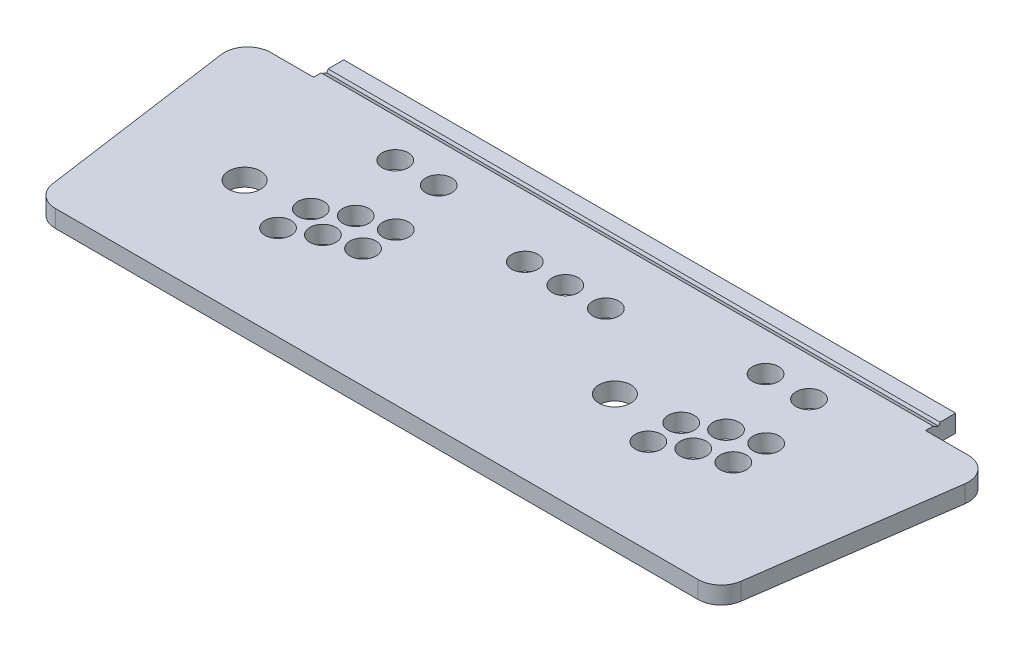
SolidWorks part; units mm, degrees
ref_plane "Front Plane" through (0, 0, 0) normal (0, 0, 1) x (1, 0, 0)
ref_plane "Top Plane" through (0, 0, 0) normal (0, 1, 0) x (1, 0, 0)
ref_plane "Right Plane" through (0, 0, 0) normal (1, 0, 0) x (0, 0, -1)
sketch "Sketch1" plane through (0, 0, 0) normal (0, 1, 0) x (1, 0, 0)
  line L9 (335.7562, 149.733) -> (-335.7563, 149.733)
  line L10 (335.7562, 149.733) -> (335.7562, -149.733)
  line L11 (335.7562, -149.733) -> (-335.7562, -149.733)
  line L12 (-335.7563, 149.733) -> (-335.7562, -149.733)
  line L13 (335.7562, 149.733) -> (-335.7562, -149.733) construction
  line L14 (335.7562, -149.733) -> (-335.7563, 149.733) construction
  point P0 (0, 0)
  dimension "D1" = 299.466
  dimension "D2" = 671.5125
extrude "Boss-Extrude1" add sketch "Sketch1" along normal mid plane 19.05
sketch "Sketch2" plane through (0, 9.525, 0) normal (0, 1, 0) x (1, 0, 0)
  line L0 (335.7562, -149.733) -> (374.6439, -149.733)
  line L1 (374.6439, -149.733) -> (412.0832, 116.6621)
  line L2 (412.0832, 116.6621) -> (335.7562, 116.6621)
  line L3 (335.7562, -149.733) -> (335.7562, 149.733) construction
  line L4 (335.7562, 116.6621) -> (335.7562, -149.733)
  line L5 (412.0832, 116.6621) -> (412.0833, -148.5139) construction
  line L6 (0, 0) -> (0, 149.733) construction
  line L7 (335.7562, 149.733) -> (-335.7563, 149.733) construction
  line L8 (-412.0832, 116.6621) -> (-412.0833, -148.5139) construction
  line L9 (-335.7562, 116.6621) -> (-335.7562, -149.733)
  line L10 (-412.0832, 116.6621) -> (-335.7562, 116.6621)
  line L11 (-374.6439, -149.733) -> (-412.0832, 116.6621)
  line L12 (-335.7562, -149.733) -> (-374.6439, -149.733)
  dimension "D1" = 266.3951
  dimension "D2" = 76.327
  dimension "D3" = 8
  dimension "D4" = 824.1665
extrude "Boss-Extrude2" add sketch "Sketch2" against normal up to surface (19.05 mm away) up to face at (0, -9.525, 0)
fillet "Fillet1" radius 25.4 4 edges at (-412.0832, 0, -116.6621) (-374.6439, 0, 149.733) (412.0832, 0, -116.6621) (374.6439, 0, 149.733)
sketch "Sketch3" plane through (0, 9.525, 0) normal (0, 1, 0) x (1, 0, 0)
  line L0 (-212.087, -46.05) -> (-212.087, -10.05) construction
  line L1 (-180.837, -28.05) -> (-180.837, 7.95) construction
  line L2 (-145.837, -19.05) -> (-145.837, 16.95) construction
  line L3 (-145.837, -19.05) -> (-145.837, -46.05) construction
  line L4 (-180.837, -28.05) -> (-180.837, -46.05) construction
  line L5 (-212.087, -46.05) -> (-180.837, -46.05) construction
  line L6 (-275.837, -19.05) -> (130.563, -19.05) construction
  line L7 (-180.837, -46.05) -> (-145.837, -46.05) construction
  line L8 (-212.087, 82.55) -> (-164.3697, 82.55) construction
  line L9 (-275.837, -19.05) -> (-275.837, 82.55) construction
  line L10 (-145.837, -46.05) -> (-128.5613, -46.05) construction
  line L11 (-212.087, -46.05) -> (-275.837, -46.05) construction
  line L12 (-275.837, 82.55) -> (-212.087, 82.55) construction
  line L13 (-275.837, -19.05) -> (-275.837, -46.05) construction
  line L14 (194.313, -46.05) -> (194.313, -10.05) construction
  line L15 (225.563, -28.05) -> (225.563, 7.95) construction
  line L16 (260.563, -19.05) -> (260.563, 16.95) construction
  line L17 (260.563, -19.05) -> (260.563, -46.05) construction
  line L18 (225.563, -28.05) -> (225.563, -46.05) construction
  line L19 (194.313, -46.05) -> (225.563, -46.05) construction
  line L20 (225.563, -46.05) -> (260.563, -46.05) construction
  line L21 (194.313, 82.55) -> (242.0303, 82.55) construction
  line L22 (130.563, -19.05) -> (130.563, 82.55) construction
  line L23 (194.313, -46.05) -> (130.563, -46.05) construction
  line L24 (130.563, 82.55) -> (194.313, 82.55) construction
  line L25 (130.563, -19.05) -> (130.563, -46.05) construction
  line L26 (-44.45, 57.15) -> (44.45, 57.15) construction
  line L27 (-275.837, -19.05) -> (-275.837, -71.5396) construction
  line L28 (-275.837, -71.5396) -> (-147.2857, -71.5396) construction
  line L29 (-147.2857, -71.5396) -> (-147.2857, -19.05) construction
  line L30 (130.563, -19.05) -> (130.563, -71.5396) construction
  line L31 (130.563, -71.5396) -> (292.5596, -71.5396) construction
  line L32 (-211.5613, -71.5396) -> (-211.5613, -17.7133) construction
  line L33 (211.5613, -71.5396) -> (211.5613, -17.7133) construction
  line L34 (0, -80.6856) -> (0, 57.15) construction
  line L36 (-243.037, 18.9) -> (-308.637, 18.9) construction
  line L37 (-243.037, 18.9) -> (-243.037, -57) construction
  line L38 (-243.037, -57) -> (-308.637, -57) construction
  line L39 (-308.637, 18.9) -> (-308.637, -57) construction
  line L40 (-243.037, 18.9) -> (-308.637, -57) construction
  line L41 (-243.037, -57) -> (-308.637, 18.9) construction
  line L42 (163.363, 18.9) -> (97.763, 18.9) construction
  line L43 (163.363, 18.9) -> (163.363, -57) construction
  line L44 (163.363, -57) -> (97.763, -57) construction
  line L45 (97.763, 18.9) -> (97.763, -57) construction
  line L46 (163.363, 18.9) -> (97.763, -57) construction
  line L47 (163.363, -57) -> (97.763, 18.9) construction
  circle A0 centre (-275.837, -19.05) radius 17.5
  circle A1 centre (-180.837, 7.95) radius 14.2875
  circle A2 centre (-145.837, 16.95) radius 14.2875
  circle A3 centre (-145.837, -19.05) radius 14.2875
  circle A4 centre (-180.837, -28.05) radius 14.2875
  circle A5 centre (-212.087, -10.05) radius 14.2875
  circle A6 centre (-212.087, -46.05) radius 14.2875
  circle A7 centre (-212.087, 82.55) radius 14.2875
  circle A8 centre (-164.3697, 82.55) radius 14.2875
  circle A9 centre (130.563, -19.05) radius 17.5
  circle A10 centre (225.563, 7.95) radius 14.2875
  circle A11 centre (260.563, 16.95) radius 14.2875
  circle A12 centre (260.563, -19.05) radius 14.2875
  circle A13 centre (225.563, -28.05) radius 14.2875
  circle A14 centre (194.313, -10.05) radius 14.2875
  circle A15 centre (194.313, -46.05) radius 14.2875
  circle A16 centre (194.313, 82.55) radius 14.2875
  circle A17 centre (242.0303, 82.55) radius 14.2875
  circle A21 centre (-308.637, 18.9) radius 3.9688
  circle A22 centre (-243.037, 18.9) radius 3.9687
  circle A23 centre (-308.637, -57) radius 3.9688
  circle A24 centre (-243.037, -57) radius 3.9687
  circle A25 centre (97.763, 18.9) radius 3.9687
  circle A26 centre (163.363, 18.9) radius 3.9687
  circle A27 centre (97.763, -57) radius 3.9688
  circle A28 centre (163.363, -57) radius 3.9687
  circle A30 centre (-44.45, 57.15) radius 14.2875
  circle A32 centre (0, 57.15) radius 14.2875
  circle A33 centre (44.45, 57.15) radius 14.2875
  point P62 (0, 57.15)
  dimension "D1" = 28.575
  dimension "D8" = 35
  dimension "D17" = 7.9375
  dimension "D18" = 65.6
  dimension "D13" = 76.2
  dimension "D12" = 88.9
  dimension "D2" = 35
  dimension "D3" = 31.25
  dimension "D4" = 18
  dimension "D5" = 9
  dimension "D6" = 36
  dimension "D7" = 95
  dimension "D9" = 47.7173
  dimension "D10" = 101.6
  dimension "D11" = 63.75
  dimension "D14" = 406.4
  dimension "D15" = 25.4896
  dimension "D19" = 75.9
  dimension "D20" = 19.05
  dimension "D21" = 130.563
extrude "Cut-Extrude1" cut sketch "Sketch3" against normal through all both and the other way through all contours A11 | A17 | A1 | A5 | A12 | A11 | A16 | A10 | A14 | A13 | A15 | A9 | A33 | A32 | A30 | A8 | A7 | A2 | A4 | A3 | A6 | A0 region at (-180.837, 9.525, -7.95) region at (-212.087, 9.525, 10.05) region at (260.563, 9.525, -16.95) region at (242.0303, 9.525, -82.55)
sketch "Sketch4" plane through (0, -9.525, 0) normal (0, -1, 0) x (1, 0, 0)
  line L0 (-346.075, -48.5201) -> (-346.075, 91.1799) construction
  line L2 (-352.564, 149.733) -> (352.564, 149.733) construction
  line L3 (-355.727, -48.5201) -> (-355.727, 91.1799)
  line L4 (-336.423, -48.5201) -> (-336.423, 91.1799)
  line L5 (0, 0) -> (0, 80.9611) construction
  line L7 (346.075, -48.5201) -> (346.075, 91.1799) construction
  line L8 (355.727, -48.5201) -> (355.727, 91.1799)
  line L9 (336.423, -48.5201) -> (336.423, 91.1799)
  arc A0 (-355.727, -48.5201) -> (-336.423, -48.5201) centre (-346.075, -48.5201) ccw
  arc A1 (-336.423, 91.1799) -> (-355.727, 91.1799) centre (-346.075, 91.1799) ccw
  arc A2 (355.727, -48.5201) -> (336.423, -48.5201) centre (346.075, -48.5201) cw
  arc A3 (336.423, 91.1799) -> (355.727, 91.1799) centre (346.075, 91.1799) cw
  point P6 (-346.075, 21.3299)
  point P18 (346.075, 21.3299)
  dimension "D1" = 19.304
  dimension "D2" = 139.7
  dimension "D3" = 346.075
  dimension "D4" = 128.4031
extrude "Cut-Extrude2" cut sketch "Sketch4" against normal blind 7.9375
sketch "Sketch5" plane through (0, 0, 0) normal (1, 0, 0) x (0, 0, -1)
  line L0 (132.55, 9.525) -> (131.233, 6.35)
  line L1 (131.233, 6.35) -> (124.7672, 9.0321)
  line L2 (124.7672, 9.0321) -> (126.0842, 12.2071)
  line L3 (126.0842, 12.2071) -> (132.55, 9.525)
  line L4 (116.6621, 9.525) -> (149.733, 9.525) construction
  line L5 (149.733, 9.525) -> (149.733, -9.525) construction
  dimension "D1" = 67.471
  dimension "D2" = 3.175
  dimension "D3" = 17.183
  dimension "D4" = 7
extrude "Cut-Extrude3" cut sketch "Sketch5" against normal through all both and the other way through all
sketch "Sketch6" [suppressed] plane through (0, 9.525, 0) normal (0, 1, 0) x (1, 0, 0)
  line L5 (-335.7563, 124.5996) -> (335.7562, 124.5996)
  line L10 (382.8639, 124.5996) -> (335.7562, 124.5996)
  line L11 (385.577, -128.9727) -> (415.877, 86.6225)
  line L12 (-352.564, -157.6705) -> (352.564, -157.6705)
  line L13 (-415.877, 86.6225) -> (-385.577, -128.9727)
  line L14 (-335.7563, 124.5996) -> (-382.8639, 124.5996)
  line L15 (382.8639, 124.5996) -> (335.7562, 124.5996)
  line L16 (385.577, -128.9727) -> (415.877, 86.6225)
  line L17 (-352.564, -157.6705) -> (352.564, -157.6705)
  line L18 (-415.877, 86.6225) -> (-385.577, -128.9727)
  line L19 (-335.7563, 124.5996) -> (-382.8639, 124.5996)
  arc A8 (415.877, 86.6225) -> (382.8639, 124.5996) centre (382.8639, 91.2621) ccw
  arc A9 (352.564, -157.6705) -> (385.577, -128.9727) centre (352.564, -124.333) ccw
  arc A10 (-385.577, -128.9727) -> (-352.564, -157.6705) centre (-352.564, -124.333) ccw
  arc A11 (-382.8639, 124.5996) -> (-415.877, 86.6225) centre (-382.8639, 91.2621) ccw
  arc A12 (415.877, 86.6225) -> (382.8639, 124.5996) centre (382.8639, 91.2621) ccw
  arc A13 (352.564, -157.6705) -> (385.577, -128.9727) centre (352.564, -124.333) ccw
  arc A14 (-385.577, -128.9727) -> (-352.564, -157.6705) centre (-352.564, -124.333) ccw
  arc A15 (-382.8639, 124.5996) -> (-415.877, 86.6225) centre (-382.8639, 91.2621) ccw
  dimension "D1" = 7.9375
extrude "Boss-Extrude3" [suppressed] add sketch "Sketch6" against normal blind 2.54
sketch "Sketch7" [suppressed] plane through (0, 9.525, 0) normal (0, 1, 0) x (1, 0, 0)
  line L0 (-335.7563, 124.5996) -> (-382.8639, 124.5996) construction
  line L1 (-353.1747, 124.5996) -> (394.2216, 124.5996)
  line L2 (-353.1747, 124.5996) -> (-353.1747, 211.9552)
  line L3 (-353.1747, 211.9552) -> (394.2216, 211.9552)
  line L4 (394.2216, 124.5996) -> (394.2216, 211.9552)
extrude "Cut-Extrude4" [suppressed] cut sketch "Sketch7" against normal through all both and the other way through all
extrude "Cut-Extrude5" cut sketch "Sketch3<3>" along normal blind 11.1125 from surface contours A26 | A25 | A27 | A28 | A24 | A23 | A21 | A22 starting at face at (-346.075, -9.525, 21.3299)
sketch "Sketch3<3>" plane through (0, 9.525, 0) normal (0, 1, 0) x (1, 0, 0) same geometry as "Sketch3"
sketch "Sketch8" plane through (0, -9.525, 0) normal (0, -1, 0) x (1, 0, 0)
  circle A0 centre (163.363, -18.9) radius 5.9531
  circle A1 centre (163.363, 57) radius 5.9531
  circle A2 centre (97.763, 57) radius 5.9531
  circle A3 centre (97.763, -18.9) radius 5.9531
  circle A4 centre (-243.037, -18.9) radius 5.9531
  circle A5 centre (-243.037, 57) radius 5.9531
  circle A6 centre (-308.637, 57) radius 5.9531
  circle A7 centre (-308.637, -18.9) radius 5.9531
  dimension "D1" = 11.9062
extrude "Cut-Extrude6" cut sketch "Sketch8" against normal blind 1.016
